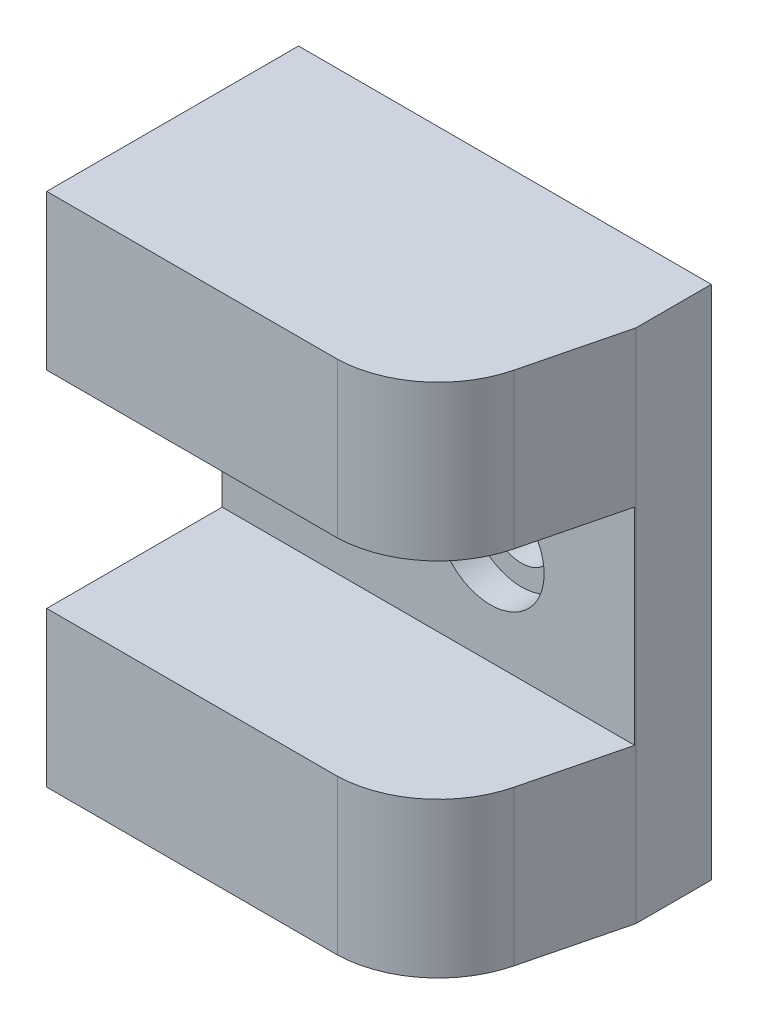
SolidWorks part; units mm, degrees
ref_plane "前视基准面" through (0, 0, 0) normal (0, 0, 1) x (1, 0, 0)
ref_plane "上视基准面" through (0, 0, 0) normal (0, 1, 0) x (1, 0, 0)
ref_plane "右视基准面" through (0, 0, 0) normal (1, 0, 0) x (0, 0, -1)
sketch "草图1" plane through (0, 0, 0) normal (0, 0, 1) x (1, 0, 0)
  line L0 (130, 105) -> (130, -105) construction
  line L1 (130, 80) -> (110, 80)
  line L2 (130, 80) -> (130, 105)
  line L4 (110, 80) -> (110, 105)
  line L5 (72, 105) -> (130, 105) construction
  line L6 (130, 105) -> (110, 105)
  dimension "D1" = 20
  dimension "D2" = 25
extrude "凸台-拉伸1" add sketch "草图1" along normal blind 12.2
sketch "草图2" plane through (0, 105, 0) normal (0, 1, 0) x (1, 0, 0)
  line L0 (130, -12.2) -> (130, 0) construction
  line L6 (128.82, -8.3843) -> (130, -3.6517)
  line L8 (130, -3.6517) -> (130, -12.2)
  line L10 (130, -12.2) -> (124.083, -12.2)
  line L11 (130, -12.2) -> (110, -12.2) construction
  arc A1 (124.083, -12.2) -> (128.82, -8.3843) centre (123.9333, -7.1659) ccw
  dimension "D1" = 5.917
extrude "切除-拉伸1" cut sketch "草图2" against normal blind 26.5
sketch "草图3" plane through (0, 0, 12.2) normal (0, 0, 1) x (1, 0, 0)
  line L0 (110, 92.5) -> (130, 92.5) construction
  line L1 (110, 105) -> (110, 80) construction
  line L4 (110, 97.5) -> (130, 97.5)
  line L5 (110, 97.5) -> (110, 87.5)
  line L6 (110, 87.5) -> (130, 87.5)
  line L7 (130, 97.5) -> (130, 87.5)
  line L8 (110, 97.5) -> (130, 87.5) construction
  line L9 (110, 87.5) -> (130, 97.5) construction
  point P6 (120, 92.5)
  dimension "D1" = 10
  dimension "D2" = 20
extrude "切除-拉伸2" cut sketch "草图3" against normal blind 8.5
sketch "草图4" plane through (0, 0, 3.7) normal (0, 0, 1) x (1, 0, 0)
  line L0 (110, 92.5) -> (129.988, 92.5) construction
  line L1 (110, 97.5) -> (110, 87.5) construction
  line L2 (129.988, 87.5) -> (129.988, 97.5) construction
  circle A0 centre (115, 92.5) radius 1.5
  circle A2 centre (123, 92.5) radius 1.5
  dimension "D1" = 3
  dimension "D2" = 8
  dimension "D3" = 5
hole_wizard "M3 六角头螺栓的柱形沉头孔1" positions "草图7" profile "草图8" counterbore size "M3" standard "GB" end condition through all
sketch "草图7" plane through (0, 0, 3.7) normal (0, 0, 1) x (1, 0, 0)
  point P0 (115, 92.5)
  point P3 (123, 92.5)
sketch "草图8" plane through (115, 92.5, 3.7) normal (1, 0, 0) x (0, -1, 0)
  line L0 (0, 0) -> (0, 3.7)
  line L1 (0, 3.7) -> (1.6, 3.7)
  line L3 (1.6, 3.7) -> (1.6, 1.5)
  line L4 (1.6, 1.5) -> (2.6, 1.5)
  line L5 (2.6, 1.5) -> (2.6, 0)
  line L7 (2.6, 0) -> (0, 0)
  line L11 (0, -6.35) -> (0, 107.95) construction
  dimension "通孔孔直径" = 3.2
  dimension "通孔孔深度" = 3.7
  dimension "柱形沉头孔直径" = 5.2
  dimension "柱形沉头孔深度" = 1.5
move or copy body "实体-移动/复制1" [suppressed] bodies to move or copy 109
